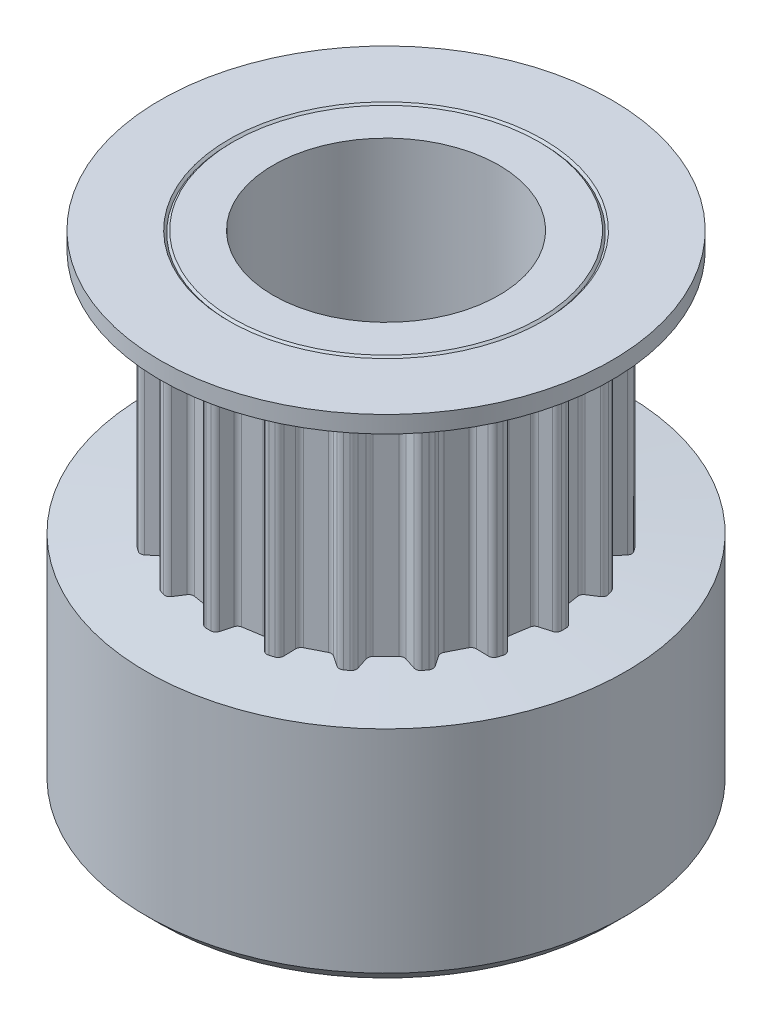
SolidWorks part; units mm, degrees
material "1060 Alloy"
ref_plane "Front Plane" through (0, 0, 0) normal (0, 0, 1) x (1, 0, 0)
ref_plane "Top Plane" through (0, 0, 0) normal (0, 1, 0) x (1, 0, 0)
ref_plane "Right Plane" through (0, 0, 0) normal (1, 0, 0) x (0, 0, -1)
ref_axis "Rotation Axis" through (0, -0.9, 0) along (0, 1, 0)
sketch "Sketch1" plane through (0, 0, 0) normal (1, 0, 0) x (0, 0, -1)
  line L0 (0, -99.3084) -> (0, 91.325) construction
  line L1 (4, -8.65) -> (4, 8.65)
  line L2 (8.5, -8.15) -> (8.5, -0.65)
  line L3 (8, -8.65) -> (8.5, -8.15)
  line L4 (8.5, -0.65) -> (5.5, -0.3875)
  line L5 (5.5, 7.8313) -> (8, 8.05)
  line L6 (8, 8.05) -> (8, 8.65)
  line L7 (8, 8.65) -> (5.575, 8.65)
  line L8 (4, -8.65) -> (8, -8.65)
  line L9 (5.5, 7.8313) -> (5.5, -0.3875)
  line L10 (5.425, 8.65) -> (5.5, 8.575)
  line L11 (5.5, 8.575) -> (5.575, 8.65)
  line L12 (5.425, 8.65) -> (4, 8.65)
  line L13 (4, 0) -> (0, 0) construction
  dimension "D2" = 11
  dimension "D3" = 16
  dimension "D4" = 8.7
  dimension "D5" = 0.5
  dimension "D6" = 0.5
  dimension "D7" = 0.6
  dimension "D8" = 8
  dimension "D9" = 17.3
  dimension "D10" = 95
  dimension "D11" = 95
  dimension "D12" = 17
  dimension "D13" = 11
  dimension "D14" = 0.15
revolve "Profile" add sketch "Sketch1" angle 360 about L0
ref_plane "Tooth Mid Plane" through (0, 3.7, 0) normal (0, 1, 0) x (1, 0, 0)
sketch "Sketch5" plane through (0, 3.7, 0) normal (0, -1, 0) x (-1, 0, 0)
  line L0 (-0.5655, 5.6815) -> (-1.2178, 5.5782)
  line L1 (-0.2705, 6.1711) -> (-0.4101, 5.8073)
  line L2 (0.4101, 5.8073) -> (0.2705, 6.1711)
  line L3 (-0.5655, 5.6815) -> (0, 0) construction
  line L4 (0, 0) -> (0.5655, 5.6815) construction
  line L5 (-0.0838, 6.0994) -> (0.0838, 6.0994) construction
  line L6 (-0.5968, 5.879) -> (0.5968, 5.879) construction
  line L7 (-0.3403, 5.9892) -> (0.3403, 5.9892) construction
  line L8 (0, 6.3) -> (0, 6.0994) construction
  line L9 (0, 6.0994) -> (0, 5.9892) construction
  line L10 (0, 5.9892) -> (0, 5.879) construction
  line L11 (0.5655, 5.6815) -> (-0.5655, 5.6815) construction
  line L12 (1.2178, 5.5782) -> (0.5655, 5.6815) construction
  line L13 (0, 5.8073) -> (0, 5.7096) construction
  line L14 (0, 5.7096) -> (0, 5.6815) construction
  line L15 (0, 5.6815) -> (0, 5.5782) construction
  line L16 (-0.4101, 5.8073) -> (0.4101, 5.8073) construction
  line L17 (0, 5.8073) -> (0, 5.879) construction
  line L18 (1.2178, 5.5782) -> (-1.2178, 5.5782) construction
  line L19 (0, 5.5782) -> (0, 0) construction
  line L20 (-0.8917, 5.6298) -> (0, 0) construction
  line L21 (0, 0) -> (0.8917, 5.6298) construction
  line L22 (1.2178, 5.5782) -> (0, 0) construction
  line L23 (0, 0) -> (-1.2178, 5.5782) construction
  line L24 (-1.2178, 5.5782) -> (-1.0665, 4.8849)
  line L25 (0.5655, 5.6815) -> (0.4952, 4.9754)
  line L26 (-0.4101, 5.8073) -> (-0.4546, 5.6914) construction
  line L28 (0.4101, 5.8073) -> (0.4546, 5.6914) construction
  arc A0 (-0.5655, 5.6815) -> (-0.4101, 5.8073) centre (-0.5968, 5.879) ccw
  arc A1 (-0.0865, 6.2994) -> (-0.2705, 6.1711) centre (-0.0838, 6.0994) ccw
  arc A2 (0.0865, 6.2994) -> (-0.0865, 6.2994) centre (0, 0) ccw
  arc A3 (0.2705, 6.1711) -> (0.0865, 6.2994) centre (0.0838, 6.0994) ccw
  arc A4 (0.4101, 5.8073) -> (0.5655, 5.6815) centre (0.5968, 5.879) ccw
  arc A5 (-1.2178, 5.5782) -> (1.2178, 5.5782) centre (0, 0) cw construction
  arc A6 (-1.0665, 4.8849) -> (0.4952, 4.9754) centre (0, 0) cw
  dimension "D3" = 0.2
  dimension "D4" = 18
  dimension "D1" = 6.3
  dimension "D2" = 5.7
  dimension "D6" = 5
  dimension "D5" = 42
  dimension "D7" = 0.1675
extrude "Tooth" add sketch "Sketch5" along normal mid plane 8.7
pattern_circular "Tooth Pattern" count 20 over 360 about axis through (0, -0.9, 0) along (0, 1, 0) of "Tooth"
ref_plane "Setscrew Plane" through (0, 0, -8.5) normal (0, 0, -1) x (-1, 0, 0)
sketch "Setscrew Point" plane through (0, 0, -8.5) normal (0, 0, -1) x (-1, 0, 0)
  line L0 (0, -0.65) -> (0, -8.65) construction
  line L1 (-8.5, -0.65) -> (8.5, -0.65) construction
  line L2 (-8, -8.65) -> (8, -8.65) construction
  point P5 (0, -4.65)
hole_wizard "M3x0.5 Setscew Hole" positions "Sketch8" profile "Sketch7" tap size "M3x0.5" standard "ANSI Metric" end condition up to next
sketch "Sketch8" plane through (0, 0, -8.5) normal (0, 0, -1) x (-1, 0, 0)
  point P0 (0, -4.65)
sketch "Sketch7" plane through (0, -4.65, -8.5) normal (1, 0, 0) x (0, 1, 0)
  line L0 (0, 0) -> (0, 4.5)
  line L1 (0, 4.5) -> (1.25, 4.5)
  line L2 (1.25, 4.5) -> (1.25, 0)
  line L3 (4, 17) -> (-3.5, 17) construction
  line L4 (-3.5, 0) -> (4, 0) construction
  line L5 (1.25, 0) -> (0, 0)
  line L11 (0, 0) -> (0, 17) construction
  dimension "Thru Tap Drill Dia." = 2.5
  dimension "Thru Tap Drill Depth" = 4.5
cosmetic thread "Hole Thread1" parameters "D2"=3
